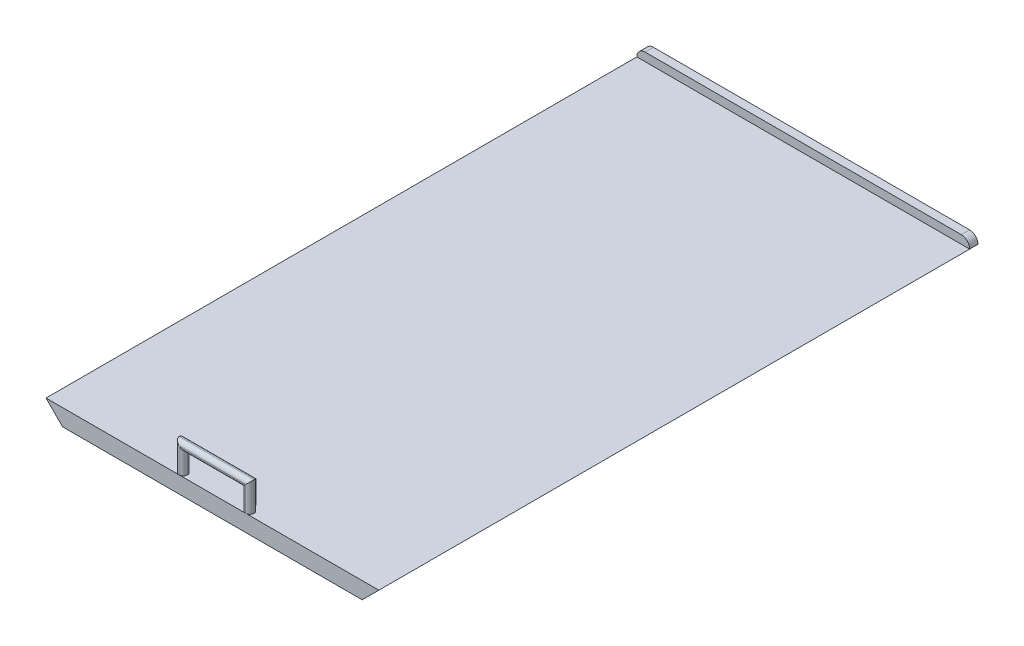
SolidWorks part; units mm, degrees
ref_plane "Front Plane" through (0, 0, 0) normal (0, 0, 1) x (1, 0, 0)
ref_plane "Top Plane" through (0, 0, 0) normal (0, 1, 0) x (1, 0, 0)
ref_plane "Right Plane" through (0, 0, 0) normal (1, 0, 0) x (0, 0, -1)
sketch "Sketch8" plane through (0, 0, 0) normal (0, 0, 1) x (1, 0, 0)
  line L0 (0, 0) -> (40, 0)
  line L1 (0, 0) -> (2, -2)
  line L2 (2, -2) -> (38, -2)
  line L3 (38, -2) -> (40, 0)
  dimension "D1" = 36
  dimension "D2" = 40
  dimension "D3" = 2
  dimension "D4" = 135
  dimension "D5" = 135
extrude "Boss-Extrude7" add sketch "Sketch8" along normal blind 72
sketch "Sketch9" plane through (0, 0, 0) normal (0, 0, -1) x (-1, 0, 0)
  line L0 (-40, 0) -> (-40, 1)
  line L1 (0, 0) -> (0, 1)
  line L2 (0, 1) -> (-40, 1)
  line L3 (0, 0) -> (-40, 0)
  dimension "D1" = 1
  dimension "D2" = 1
extrude "Boss-Extrude8" add sketch "Sketch9" against normal blind 1 separate body
fillet "Fillet2" radius 1 2 edges at (0, 1, 0.5) (40, 1, 0.5)
sketch "Sketch11" plane through (0, 0, 0) normal (0, 0, 1) x (1, 0, 0)
  line L0 (20, 1) -> (20, -2.4264) construction
  line L1 (1, 1) -> (39, 1) construction
  line L2 (20, 1) -> (20, 6) construction
  line L3 (24.5, 3.5) -> (15.5, 3.5)
  line L4 (15.5, 3.5) -> (15.5, 0)
  line L5 (40, 0) -> (0, 0) construction
  line L6 (24.5, 3.5) -> (24.5, 0)
  line L7 (15.5, 0) -> (16.5, 0)
  line L8 (24.5, 0) -> (23.5, 0)
  line L9 (23.5, 0) -> (23.5, 2.5)
  line L10 (23.5, 2.5) -> (16.5, 2.5)
  line L11 (16.5, 2.5) -> (16.5, 0)
  line L12 (40, 0) -> (0, 0) construction
  point P11 (20, 3.5)
  dimension "D1" = 1
  dimension "D2" = 3.5
  dimension "D3" = 1
  dimension "D4" = 1
  dimension "D5" = 7
  dimension "D6" = 15.5
extrude "Boss-Extrude9" add sketch "Sketch11" along normal blind 1 from offset 71
fillet "Fillet3" radius 0.5 11 edges at (16.5, 1.25, 71) (24.5, 1.75, 71) (16.5, 1.25, 72) (20, 2.5, 72) (20, 3.5, 71) (20, 3.5, 72) (23.5, 1.25, 71) (23.5, 1.25, 72) (24.5, 1.75, 72) (15.5, 1.75, 71) (15.5, 1.75, 72)
